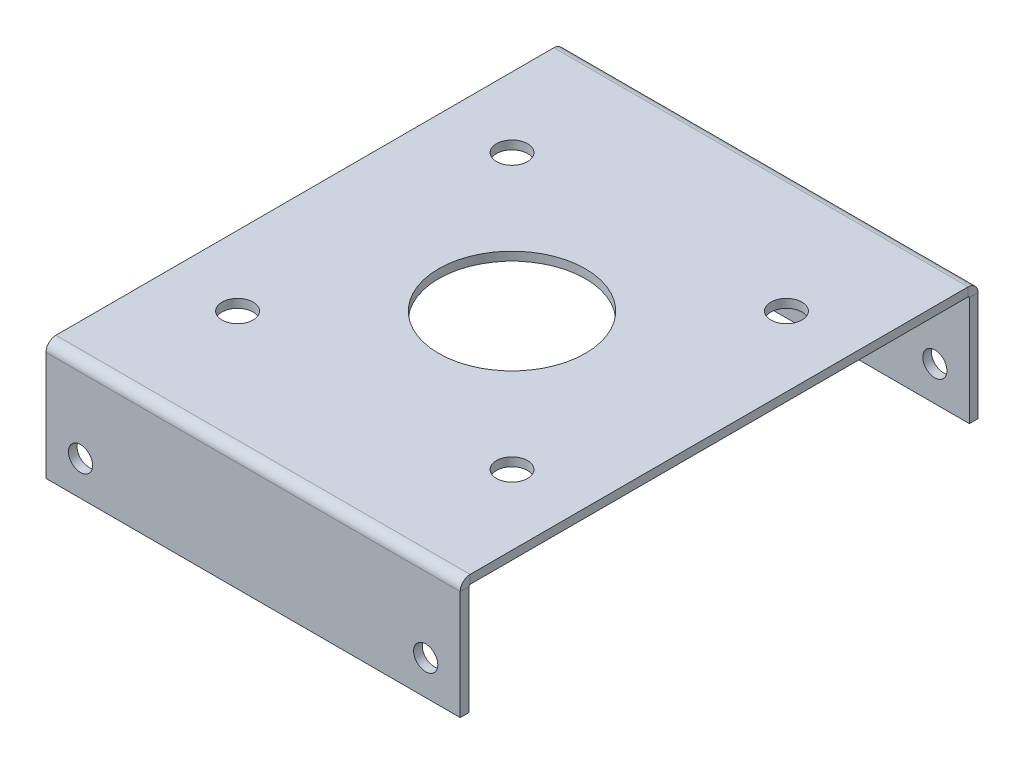
SolidWorks part; units mm, degrees
note: The reader was unsure of these and kept them because the rebuilt part matched: flange length of "Edge-Flange1".
material "ASTM A36 Steel"
ref_plane "Front Plane" through (0, 0, 0) normal (0, 0, 1) x (1, 0, 0)
ref_plane "Top Plane" through (0, 0, 0) normal (0, 1, 0) x (1, 0, 0)
ref_plane "Right Plane" through (0, 0, 0) normal (1, 0, 0) x (0, 0, -1)
sketch "Sketch1" plane through (0, 0, 0) normal (0, 1, 0) x (1, 0, 0)
  line L1 (-120, -150) -> (120, -150)
  line L2 (-120, -150) -> (-120, 150)
  line L3 (-120, 150) -> (120, 150)
  line L4 (120, -150) -> (120, 150)
  line L5 (-120, -150) -> (120, 150) construction
  line L6 (-120, 150) -> (120, -150) construction
  point P0 (0, 0)
  dimension "D1" = 300
  dimension "D2" = 240
base flange "Base-Flange1" sketch "Sketch1" thickness 5 reverse thickness direction no parameters "D1"=0.7366
edge flange "Edge-Flange1" sketch "Sketch10" flange profiles "Sketch10", "Sketch11" flange angle 90 flange length 69 flange position material inside bend radius 0.7366 thickness 5 relief rectangular parameters "D6"=10, "D8"=1
sketch "Sketch10" plane through (0, -5, -150) normal (0, 0, -1) x (1, 0, 0)
  line L0 (120, 0) -> (-120, 0) construction
  line L1 (120, 0) -> (-120, 0)
  line L2 (-120, 0) -> (-120, 64)
  line L3 (-120, 64) -> (120, 64)
  line L4 (120, 64) -> (120, 0)
sketch "Sketch11" plane through (0, -5, 150) normal (0, 0, 1) x (-1, 0, 0)
  line L0 (120, 0) -> (-120, 0) construction
  line L1 (120, 0) -> (-120, 0)
  line L2 (-120, 0) -> (-120, 64)
  line L3 (-120, 64) -> (120, 64)
  line L4 (120, 64) -> (120, 0)
bend "EdgeBend1" bend radius 0.7366 bend angle 90 parameters "D5"=1
bend "EdgeBend2" bend radius 0.7366 bend angle 90 parameters "D5"=2
sketch "Sketch12" plane through (0, 0, -150) normal (0, 0, -1) x (-1, 0, 0)
  line L0 (-120, -69) -> (120, -69) construction
  line L1 (-120, -5.7366) -> (-120, -69) construction
  line L2 (120, -69) -> (120, -5.7366) construction
  circle A0 centre (100, -49) radius 7
  circle A1 centre (-100, -49) radius 7
  dimension "D1" = 14
  dimension "D2" = 14
  dimension "D3" = 20
  dimension "D4" = 20
  dimension "D5" = 20
  dimension "D6" = 20
extrude "Cut-Extrude1" cut sketch "Sketch12" against normal through all both and the other way through all normal cut yes
sketch "Sketch13" plane through (0, 0, 0) normal (0, 1, 0) x (1, 0, 0)
  circle A0 centre (0, 0) radius 42.5
  circle A2 centre (79.5, 79.5) radius 9
  circle A3 centre (-79.5, 79.5) radius 9
  circle A4 centre (-79.5, -79.5) radius 9
  circle A5 centre (79.5, -79.5) radius 9
  dimension "D1" = 85
  dimension "D4" = 18
  dimension "D5" = 18
  dimension "D6" = 18
  dimension "D7" = 18
  dimension "D2" = 159
  dimension "D3" = 159
extrude "Cut-Extrude3" cut sketch "Sketch13" against normal blind 10 normal cut yes
sketch "Bend-Lines1" [suppressed] plane through (0, 0, 0) normal (0, 1, 0) x (1, 0, 0)
sketch "Bounding-Box1" [suppressed] plane through (0, 0, 0) normal (0, 1, 0) x (1, 0, 0)
sheet metal parameters "Sheet-Metal1" thickness 5 parameters "D1"=0.7366
flat pattern "Flat-Pattern1" [suppressed]
sketch "Bend-Lines2" plane through (0, 0, 0) normal (0, 1, 0) x (1, 0, 0)
sketch3d "Bounding-Box2" [suppressed]
  line L0 (120, -150, 0) -> (120, 150, 0) construction
  line L1 (-120, -150, 0) -> (-120, 150, 0) construction
  line L2 (120, -150, 0) -> (-120, -150, 0) construction
  line L3 (120, 150, 0) -> (-120, 150, 0) construction
sheet metal parameters "Sheet-Metal2" thickness 5 parameters "D1"=0.7366
flat pattern "Flat-Pattern1"
sketch "Bend-Lines2" plane through (0, 0, 0) normal (0, 1, 0) x (1, 0, 0)
  line L0 (-120, -146.8054) -> (120, -146.8054) construction
  line L1 (120, 146.8054) -> (-120, 146.8054) construction
  line L2 (-120, -146.8054) -> (120, -146.8054) construction
  line L3 (120, 146.8054) -> (-120, 146.8054) construction
sketch3d "Bounding-Box2" [suppressed]
  line L0 (-120, -212.6108, 0) -> (-120, 212.6108, 0) construction
  line L1 (120, -212.6108, 0) -> (120, 212.6108, 0) construction
  line L2 (-120, -212.6108, 0) -> (120, -212.6108, 0) construction
  line L3 (-120, 212.6108, 0) -> (120, 212.6108, 0) construction
bend of the flat pattern "Flatten-<EdgeBend1>1"
bend of the flat pattern "Flatten-<EdgeBend2>1"
sheet metal parameters "Sheet-Metal3" thickness 5 parameters "D1"=0.7366
flat pattern "Flat-Pattern1"
sketch "Bend-Lines2" plane through (0, 0, 0) normal (0, 1, 0) x (1, 0, 0)
  line L0 (-120, -146.8054) -> (120, -146.8054) construction
  line L1 (120, 146.8054) -> (-120, 146.8054) construction
  line L2 (-120, -146.8054) -> (120, -146.8054) construction
  line L3 (120, 146.8054) -> (-120, 146.8054) construction
sketch3d "Bounding-Box2" [suppressed]
  line L0 (-120, -212.6108, 0) -> (-120, 212.6108, 0) construction
  line L1 (120, -212.6108, 0) -> (120, 212.6108, 0) construction
  line L2 (-120, -212.6108, 0) -> (120, -212.6108, 0) construction
  line L3 (-120, 212.6108, 0) -> (120, 212.6108, 0) construction
bend of the flat pattern "Flatten-<EdgeBend1>1"
bend of the flat pattern "Flatten-<EdgeBend2>1"
sheet metal parameters "Sheet-Metal4" thickness 5 parameters "D1"=0.7366
flat pattern "Flat-Pattern1"
sketch "Bend-Lines2" plane through (0, 0, 0) normal (0, 1, 0) x (1, 0, 0)
  line L0 (-120, -146.8054) -> (120, -146.8054) construction
  line L1 (120, 146.8054) -> (-120, 146.8054) construction
  line L2 (-120, -146.8054) -> (120, -146.8054) construction
  line L3 (120, 146.8054) -> (-120, 146.8054) construction
sketch3d "Bounding-Box2" [suppressed]
  line L0 (-120, -212.6108, 0) -> (-120, 212.6108, 0) construction
  line L1 (120, -212.6108, 0) -> (120, 212.6108, 0) construction
  line L2 (-120, -212.6108, 0) -> (120, -212.6108, 0) construction
  line L3 (-120, 212.6108, 0) -> (120, 212.6108, 0) construction
bend of the flat pattern "Flatten-<EdgeBend2>2"
bend of the flat pattern "Flatten-<EdgeBend1>2"
sheet metal parameters "Sheet-Metal5" thickness 5 parameters "D1"=0.7366
flat pattern "Flat-Pattern5"
sketch "Bend-Lines4" plane through (0, 0, 0) normal (0, 1, 0) x (1, 0, 0)
sketch3d "Bounding-Box4" [suppressed]
  line L0 (78.3875, 78.6279, 0) -> (78.6271, 80.6125, 0) construction
  line L1 (80.3717, 78.3882, 0) -> (80.6114, 80.3728, 0) construction
  line L2 (78.3875, 78.6279, 0) -> (80.3717, 78.3882, 0) construction
  line L3 (78.6271, 80.6125, 0) -> (80.6114, 80.3728, 0) construction
